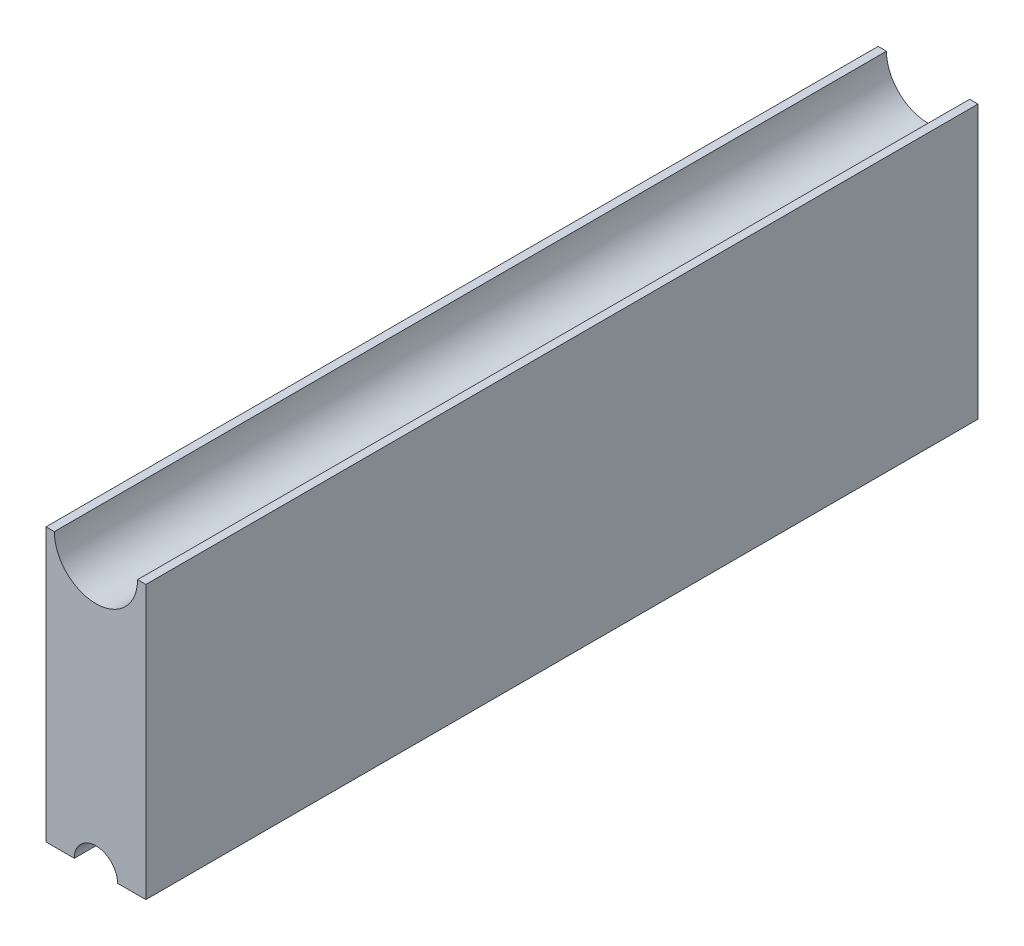
SolidWorks part; units mm, degrees
ref_plane "Front Plane" through (0, 0, 0) normal (0, 0, 1) x (1, 0, 0)
ref_plane "Top Plane" through (0, 0, 0) normal (0, 1, 0) x (1, 0, 0)
ref_plane "Right Plane" through (0, 0, 0) normal (1, 0, 0) x (0, 0, -1)
sketch "Sketch1" plane through (0, 0, 0) normal (0, 0, 1) x (1, 0, 0)
  line L16 (-5.207, -8.382) -> (-12.827, -8.382)
  line L17 (-5.207, -8.382) -> (-5.207, -29.21)
  line L18 (-12.827, -8.382) -> (-12.827, -29.21)
  line L19 (-5.207, -29.21) -> (-12.827, -29.21)
  circle A0 centre (-9.017, -8.382) radius 3.175
  circle A1 centre (-9.017, -29.21) radius 1.651
  dimension "D9" = 6.35
  dimension "D10" = 3.302
  dimension "D2" = 20.828
  dimension "D3" = 7.62
  dimension "D4" = 3.81
  dimension "D11" = 20.828
extrude "Boss-Extrude4" add sketch "Sketch1" along normal blind 63.5 contours A1 L19 L17 A0 L18 region at (-9.017, -19.5318, 0)
